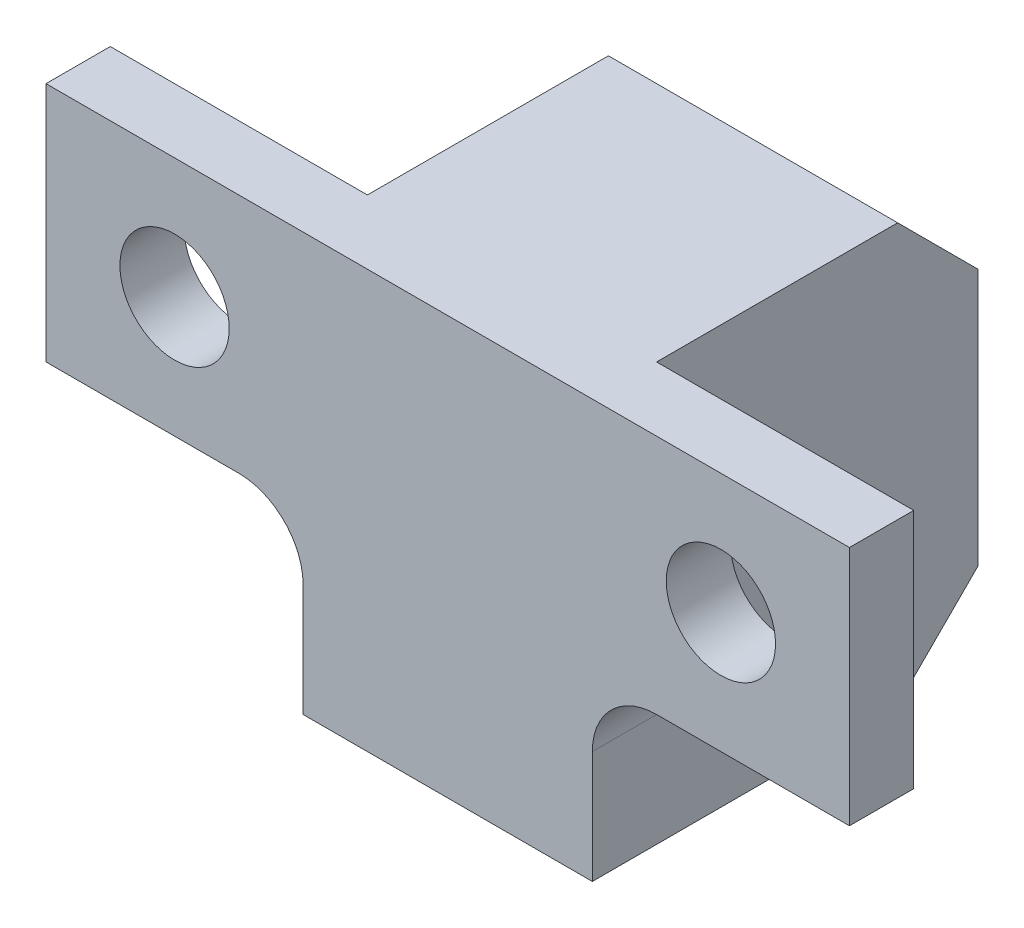
SolidWorks part; units mm, degrees
material "6061 Alloy"
ref_plane "Front Plane" through (0, 0, 0) normal (0, 0, 1) x (1, 0, 0)
ref_plane "Top Plane" through (0, 0, 0) normal (0, 1, 0) x (1, 0, 0)
ref_plane "Right Plane" through (0, 0, 0) normal (1, 0, 0) x (0, 0, -1)
sketch "Sketch1" plane through (0, 0, 0) normal (0, 1, 0) x (1, 0, 0)
  line L0 (0, 0) -> (8, 0)
  line L1 (8, 0) -> (8, 10)
  line L2 (8, 10) -> (17, 10)
  line L3 (17, 10) -> (17, 0)
  line L4 (17, 0) -> (25, 0)
  line L5 (25, 0) -> (25, -2)
  line L6 (25, -2) -> (0, -2)
  line L7 (0, -2) -> (0, 0)
  dimension "D1" = 2
  dimension "D2" = 12
  dimension "D3" = 8
  dimension "D4" = 8
  dimension "D5" = 9
extrude "Boss-Extrude1" add sketch "Sketch1" along normal blind 15 contours L1 L2 L3 L4 L5 L6 L7 L0
sketch "Sketch5" plane through (0, 0, 0) normal (0, 0, -1) x (-1, 0, 0)
  line L0 (-25, 7.5) -> (-17, 7.5)
  line L1 (-25, 15) -> (-25, 0) construction
  line L2 (-17, 15) -> (-17, 0) construction
  line L4 (-17, 15) -> (-17, 0) construction
  line L5 (-17, 0) -> (-25, 0)
  line L6 (-25, 0) -> (-25, 7.5)
  line L7 (-8, 7.5) -> (0, 7.5)
  line L8 (-8, 15) -> (-8, 0) construction
  line L9 (0, 15) -> (0, 0) construction
  line L10 (0, 7.5) -> (0, 0)
  line L11 (0, 0) -> (-8, 0)
  line L12 (-8, 0) -> (-17, 0) construction
  line L13 (0, 0) -> (-8, 0) construction
  line L14 (-17, 2) -> (-8, 2)
  line L16 (-17, 7.5) -> (-17, 2)
  line L17 (-8, 7.5) -> (-8, 2)
  line L18 (-17, 0) -> (-8, 0)
  dimension "D1" = 2
extrude "Cut-Extrude2" cut sketch "Sketch5" against normal through all both and the other way through all
sketch "Sketch6" plane through (0, 0, -10) normal (0, 0, -1) x (-1, 0, 0)
  line L0 (-17, 15) -> (-17, 7.5)
  line L1 (-17, 7.5) -> (-8, 7.5)
  line L2 (-8, 7.5) -> (-8, 15)
  line L3 (-8, 15) -> (-8, 7.5) construction
  line L4 (-8, 15) -> (-8, 2) construction
  line L5 (-8, 15) -> (-17, 15)
hole_wizard "M3 Clearance Hole1" positions "Sketch2" profile "Sketch3" hole size "M3" standard "ANSI Metric"
sketch "Sketch2" plane through (0, 0, 0) normal (0, 0, -1) x (-1, 0, 0)
  line L1 (-17, 7.5) -> (-25, 7.5) construction
  line L2 (-25, 15) -> (-25, 7.5) construction
  point P0 (-4, 11.25)
  point P2 (-21, 11.25)
  dimension "D1" = 17
  dimension "D2" = 3.75
  dimension "D3" = 4
sketch "Sketch3" plane through (4, 11.25, 0) normal (1, 0, 0) x (0, 1, 0)
  line L0 (0, 0) -> (0, 4.9215)
  line L1 (0, 4.9215) -> (1.7, 3.9)
  line L2 (1.7, 3.9) -> (1.7, 0)
  line L5 (1.7, 0) -> (0, 0)
  line L10 (0, 4.9215) -> (-1.7, 3.9) construction
  line L11 (0, -6.35) -> (0, 107.95) construction
  dimension "Hole Dia." = 3.4
  dimension "Hole Depth" = 3.9
  dimension "Drill Angle" = 118
hole_wizard "Tap Drill for M3x0.5 Tap1" positions "Sketch7" profile "Sketch8" hole size "M3x0.5" standard "ANSI Metric" end condition through all
sketch "Sketch7" plane through (8, 0, 0) normal (-1, 0, 0) x (0, 0, 1)
  line L0 (2, 2) -> (2, 7.5) construction
  line L2 (2, 7.5) -> (0, 7.5) construction
  point P0 (-6, 5.25)
  dimension "D1" = 8
  dimension "D2" = 2.25
sketch "Sketch8" plane through (8, 5.25, -6) normal (0, 1, 0) x (0, 0, 1)
  line L0 (0, 0) -> (0, 17)
  line L1 (0, 17) -> (1.25, 17)
  line L2 (1.25, 17) -> (1.25, 0)
  line L5 (1.25, 0) -> (0, 0)
  line L11 (0, -6.35) -> (0, 107.95) construction
  dimension "Thru Hole Dia." = 2.5
  dimension "Thru Hole Depth" = 17
chamfer "Chamfer2" distance 2.5 angle 45 2 edges at (12.5, 15, -10) (12.5, 2, -10)
fillet "Fillet1" radius 2 2 edges at (17, 7.5, 1) (8, 7.5, 1)
